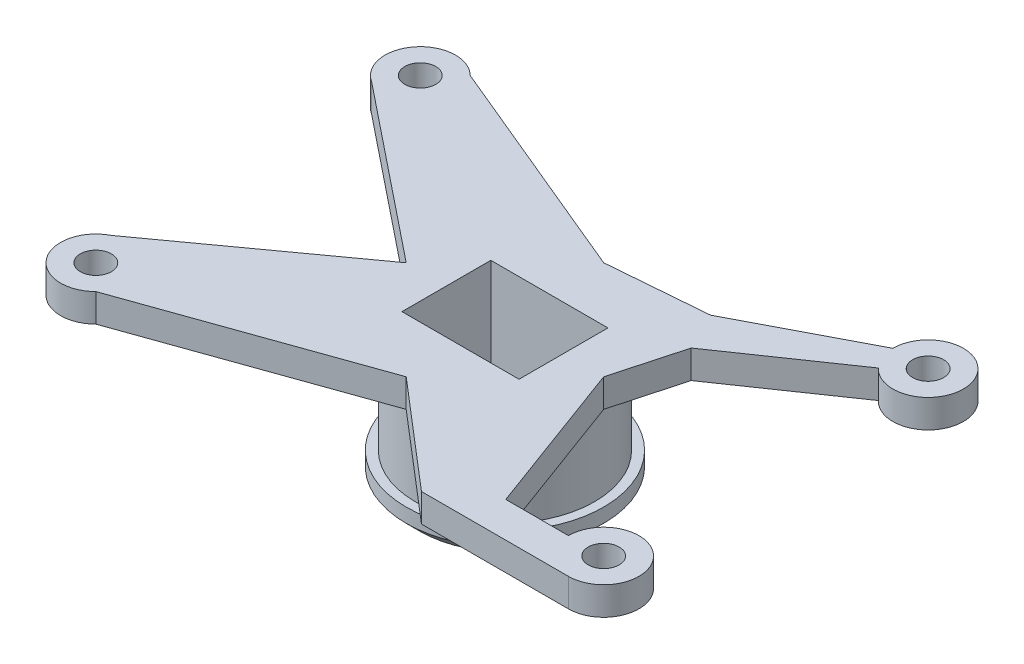
SolidWorks part; units mm, degrees
ref_plane "Front Plane" through (0, 0, 0) normal (0, 0, 1) x (1, 0, 0)
ref_plane "Top Plane" through (0, 0, 0) normal (0, 1, 0) x (1, 0, 0)
ref_plane "Right Plane" through (0, 0, 0) normal (1, 0, 0) x (0, 0, -1)
sketch "Sketch1" plane through (0, 0, 0) normal (0, 1, 0) x (1, 0, 0)
  circle A0 centre (0, 0) radius 6.35
  dimension "D1" = 12.7
extrude "Boss-Extrude1" add sketch "Sketch1" against normal blind 5
sketch "Sketch2" plane through (0, 0, 0) normal (0, 1, 0) x (1, 0, 0)
  circle A0 centre (0, 0) radius 7
  dimension "D1" = 14
extrude "Boss-Extrude2" add sketch "Sketch2" along normal blind 2
extrude "Boss-Extrude3" add sketch "Sketch2<2>" against normal blind 2 from surface starting at face at (0, -5, 6.35)
sketch "Sketch2<2>" plane through (0, 0, 0) normal (0, 1, 0) x (1, 0, 0) same geometry as "Sketch2"
chamfer "Chamfer1" distance 1 angle 45 2 edges at (0, 0, 7) (0, -7, 7)
sketch "Sketch3" plane through (0, -7, 0) normal (0, -1, 0) x (1, 0, 0)
  line L1 (-4.15, -3.15) -> (4.15, -3.15)
  line L2 (-4.15, -3.15) -> (-4.15, 3.15)
  line L3 (-4.15, 3.15) -> (4.15, 3.15)
  line L4 (4.15, -3.15) -> (4.15, 3.15)
  line L5 (-4.15, -3.15) -> (4.15, 3.15) construction
  line L6 (-4.15, 3.15) -> (4.15, -3.15) construction
  point P0 (0, 0)
  dimension "D1" = 8.3
  dimension "D2" = 6.3
extrude "Cut-Extrude1" cut sketch "Sketch3" against normal through all
sketch "Sketch4" plane through (0, 2, 0) normal (0, 1, 0) x (1, 0, 0)
  line L0 (0, 0) -> (0, 14.5) construction
  line L1 (0, 0) -> (20.3185, 0) construction
  line L2 (20.5, 14.5) -> (-20.5, 14.5)
  line L3 (-20.5, 14.5) -> (-20.5, -13.5)
  line L4 (-20.5, -13.5) -> (20.5, -13.5)
  line L5 (20.5, -13.5) -> (20.5, 14.5)
  circle A0 centre (-18, 12) radius 1.1
  circle A1 centre (-18, -11) radius 1.1
  circle A2 centre (18, -11) radius 1.1
  circle A3 centre (18, 12) radius 1.1
  point P9 (0, 14.5)
  dimension "D4" = 36
  dimension "D5" = 2.2
  dimension "D6" = 23
  dimension "D7" = 2.5
  dimension "D8" = 2.5
  dimension "D1" = 41
  dimension "D2" = 28
  dimension "D3" = 14.5
sketch "Sketch6" plane through (0, 2, 0) normal (0, 1, 0) x (1, 0, 0)
  circle A0 centre (-18, 12) radius 1.1
  circle A1 centre (18, 12) radius 1.1
  circle A2 centre (18, -11) radius 1.1
  circle A3 centre (-18, -11) radius 1.1
  circle A4 centre (-18, -11) radius 2.5
  circle A5 centre (18, -11) radius 2.5
  circle A6 centre (18, 12) radius 2.5
  circle A7 centre (-18, 12) radius 2.5
  dimension "D1" = 5
  dimension "D2" = 2.2
extrude "Boss-Extrude4" add sketch "Sketch6" along normal blind 1 and the other way blind 1 separate body
sketch "Sketch7" plane through (0, 3, 0) normal (0, 1, 0) x (1, 0, 0)
  line L3 (-19.7678, 10.2322) -> (-16.2322, 10.2322)
  line L7 (-16.2322, 10.2322) -> (-16.2322, 13.7678)
  line L27 (15.5, -11) -> (11.058, -11)
  line L28 (-4.15, -3.15) -> (4.15, -3.15)
  line L29 (-4.15, -3.15) -> (-4.15, 3.15)
  line L30 (-4.15, 3.15) -> (4.15, 3.15)
  line L31 (4.15, -3.15) -> (4.15, 3.15)
  line L32 (-4.15, -3.15) -> (4.15, 3.15) construction
  line L33 (-4.15, 3.15) -> (4.15, -3.15) construction
  line L34 (11.058, -11) -> (7, 0)
  line L35 (0, 0) -> (20.3185, 0) construction
  line L36 (18, -13.5) -> (7.583, -13.5)
  line L37 (-20.5, -13.5) -> (20.5, -13.5) construction
  line L38 (7.583, -13.5) -> (0, -7)
  line L39 (-19.7678, -9.2322) -> (-16.2322, -9.2322)
  line L40 (-16.2322, -12.7678) -> (0, -7)
  line L41 (-19.7678, -9.2322) -> (-7, 0)
  line L42 (-19.7678, 10.2322) -> (-7, 0)
  line L43 (-16.2322, -9.2322) -> (-16.2322, -12.7678)
  line L44 (-16.2322, 13.7678) -> (0, 7)
  line L45 (0, 0) -> (0, 14.5) construction
  line L46 (0, 7) -> (7, 7.5722)
  line L47 (7, 7.5722) -> (15.5, 12)
  line L48 (7, 0) -> (8.3345, 4.8691)
  line L49 (8.3345, 4.8691) -> (16.1924, 10.2729)
  line L50 (16.1924, 10.2729) -> (15.5, 12)
  line L51 (15.5, -11) -> (18, -13.5)
  circle A5 centre (18, -11) radius 2.5 construction
  circle A6 centre (0, 0) radius 7 construction
  circle A7 centre (-18, -11) radius 2.5 construction
  circle A8 centre (-18, 12) radius 2.5 construction
  circle A9 centre (18, 12) radius 2.5 construction
  point P34 (0, 0)
  dimension "D1" = 7
  dimension "D2" = 70
extrude "Boss-Extrude5" add sketch "Sketch7" against normal up to surface (2 mm away) up to face at (-18, 1, -10.9)
